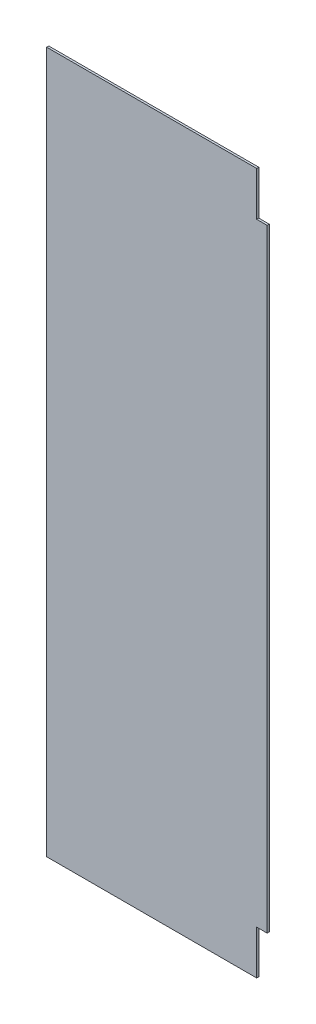
SolidWorks part; units mm, degrees
ref_plane "Спереди" through (0, 0, 0) normal (0, 0, 1) x (1, 0, 0)
ref_plane "Сверху" through (0, 0, 0) normal (0, 1, 0) x (1, 0, 0)
ref_plane "Справа" through (0, 0, 0) normal (1, 0, 0) x (0, 0, -1)
sketch "Эскиз1" plane through (0, 0, 0) normal (0, 0, 1) x (1, 0, 0)
  line L0 (23.5, 14.6) -> (24, 14.6)
  line L1 (13.5, -16.7) -> (23.5, -16.7)
  line L2 (13.5, -16.7) -> (13.5, 16.7)
  line L3 (13.5, 16.7) -> (23.5, 16.7)
  line L4 (23.5, -16.7) -> (23.5, -14.6)
  line L5 (13.5, -16.7) -> (23.5, 16.7) construction
  line L6 (13.5, 16.7) -> (23.5, -16.7) construction
  line L7 (24, -14.8) -> (24, 14.8) construction
  line L8 (24, 14.6) -> (24, -14.6)
  line L9 (-23.7, 17) -> (23.5, 17) construction
  line L10 (23.5, 17) -> (23.5, 14.8) construction
  line L11 (24, -14.6) -> (23.5, -14.6)
  line L12 (23.5, 14.6) -> (23.5, 16.7)
  line L13 (23.5, 14.8) -> (24, 14.8) construction
  point P0 (18.5, 0)
  point P14 (24, 0)
  dimension "D1" = 10
  dimension "D2" = 0.3
  dimension "D3" = 0.2
extrude "Бобышка-Вытянуть1" add sketch "Эскиз1" along normal blind 0.1
